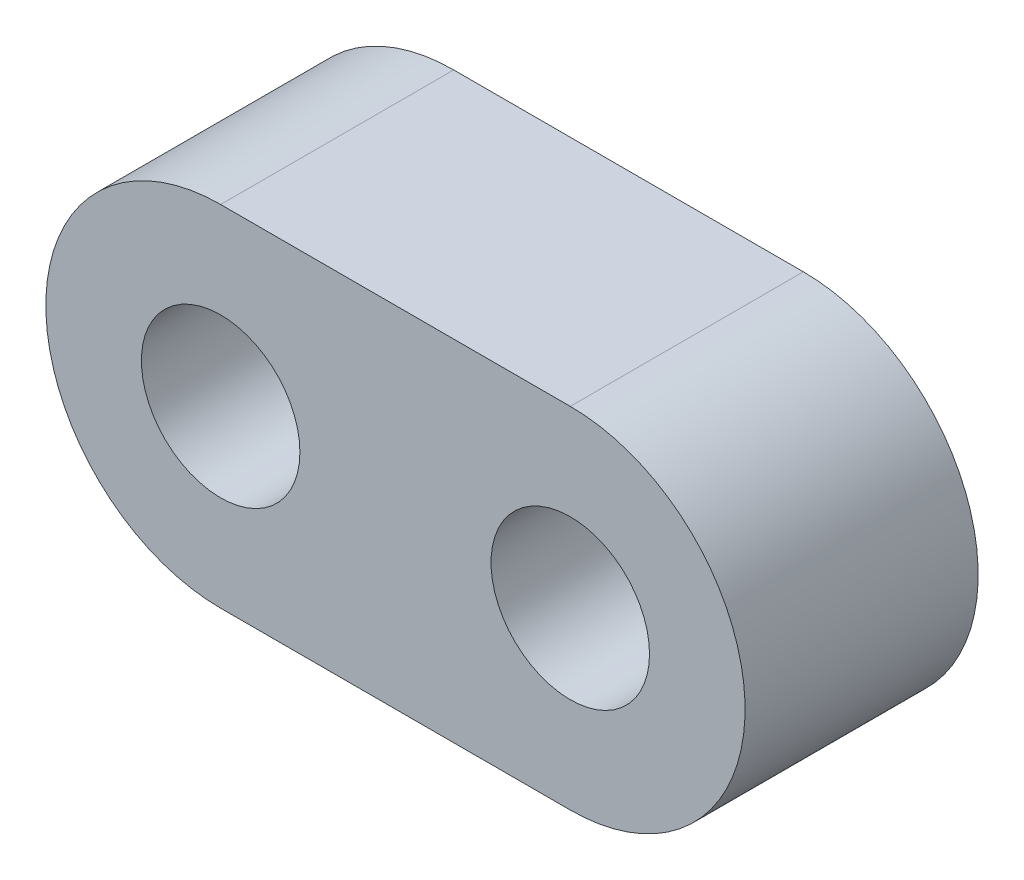
SolidWorks part; units mm, degrees
ref_plane "Front Plane" through (0, 0, 0) normal (0, 0, 1) x (1, 0, 0)
ref_plane "Top Plane" through (0, 0, 0) normal (0, 1, 0) x (1, 0, 0)
ref_plane "Right Plane" through (0, 0, 0) normal (1, 0, 0) x (0, 0, -1)
sketch "Sketch1" plane through (0, 0, 0) normal (0, 0, 1) x (1, 0, 0)
  line L0 (0, 0) -> (9.525, 0) construction
  line L1 (0, 4.7625) -> (9.525, 4.7625)
  line L2 (0, -4.7625) -> (9.525, -4.7625)
  arc A0 (0, 4.7625) -> (0, -4.7625) centre (0, 0) ccw
  arc A1 (9.525, -4.7625) -> (9.525, 4.7625) centre (9.525, 0) ccw
  circle A2 centre (9.525, 0) radius 2.159
  circle A3 centre (0, 0) radius 2.159
  point P3 (4.7625, 0)
  dimension "D2" = 9.525
  dimension "D3" = 4.318
  dimension "D1" = 9.525
extrude "Boss-Extrude1" add sketch "Sketch1" along normal blind 6.35
